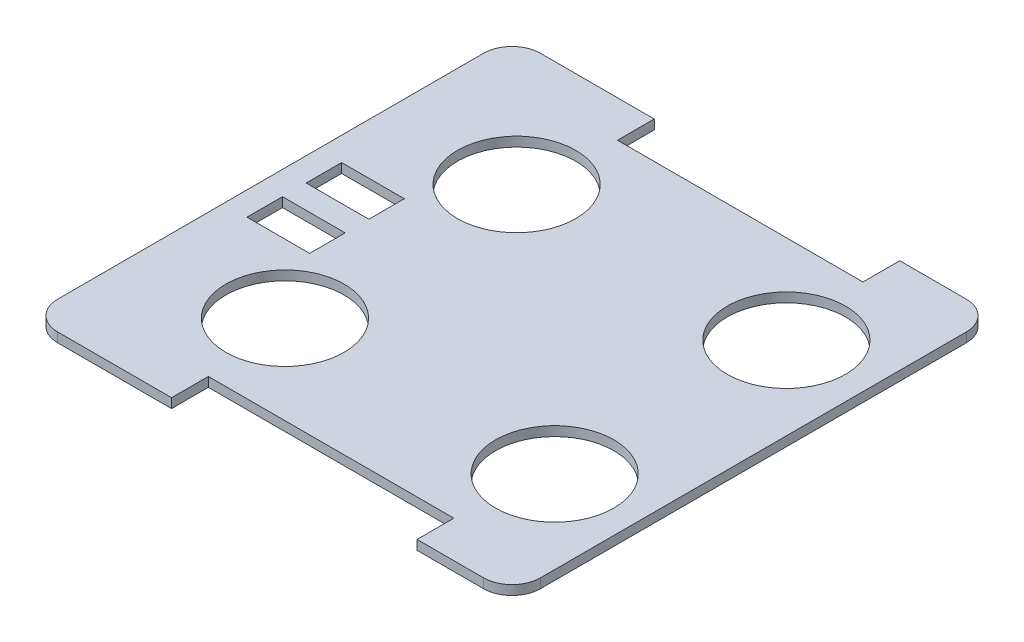
SolidWorks part; units mm, degrees
material "Aleación 1060"
ref_plane "Alzado" through (0, 0, 0) normal (0, 0, 1) x (1, 0, 0)
ref_plane "Planta" through (0, 0, 0) normal (0, 1, 0) x (1, 0, 0)
ref_plane "Vista lateral" through (0, 0, 0) normal (1, 0, 0) x (0, 0, -1)
ref_plane "Plano1" through (0, 54.7071, 0) normal (0, 1, 0) x (1, 0, 0)
sketch "Croquis1" plane through (0, 54.7071, 0) normal (0, 1, 0) x (1, 0, 0)
  line L48 (-135.857, -92.1) -> (-135.857, -55) construction
  line L55 (-135.857, -92.1) -> (71.653, -92.1) construction
  line L63 (71.653, -92.1) -> (71.653, -55) construction
  line L72 (71.653, -437.9) -> (71.653, -475) construction
  line L82 (-135.857, -437.9) -> (71.653, -437.9) construction
  line L93 (-135.857, -437.9) -> (-135.857, -475) construction
  line L105 (-232.102, -61.0045) -> (-135.857, -61.0045) construction
  line L106 (71.653, -61.0045) -> (127.898, -61.0045) construction
  line L107 (151.8935, -85) -> (151.8935, -445) construction
  line L108 (127.898, -468.9955) -> (71.653, -468.9955) construction
  line L109 (-135.857, -468.9955) -> (-232.102, -468.9955) construction
  line L110 (-256.0976, -445) -> (-256.0976, -85) construction
  line L111 (-135.857, -92.1) -> (71.653, -92.1)
  line L112 (71.653, -437.9) -> (71.653, -468.9955)
  line L113 (-135.857, -437.9) -> (71.653, -437.9)
  line L114 (-135.857, -437.9) -> (-135.857, -468.9955)
  line L115 (-135.857, -92.1) -> (-135.857, -61.0045)
  line L116 (71.653, -92.1) -> (71.653, -61.0045)
  line L117 (-232.102, -61.0045) -> (-135.857, -61.0045)
  line L118 (71.653, -61.0045) -> (127.898, -61.0045)
  line L119 (151.8935, -85) -> (151.8935, -445)
  line L120 (127.898, -468.9955) -> (71.653, -468.9955)
  line L121 (-135.857, -468.9955) -> (-232.102, -468.9955)
  line L122 (-256.0976, -445) -> (-256.0976, -85)
  arc A56 (-232.102, -61.0045) -> (-256.0976, -85) centre (-232.102, -85) ccw construction
  arc A57 (151.8935, -85) -> (127.898, -61.0045) centre (127.898, -85) ccw construction
  arc A58 (127.898, -468.9955) -> (151.8935, -445) centre (127.898, -445) ccw construction
  arc A59 (-256.0976, -445) -> (-232.102, -468.9955) centre (-232.102, -445) ccw construction
  arc A60 (-232.102, -61.0045) -> (-256.0976, -85) centre (-232.102, -85) ccw
  arc A61 (151.8935, -85) -> (127.898, -61.0045) centre (127.898, -85) ccw
  arc A62 (127.898, -468.9955) -> (151.8935, -445) centre (127.898, -445) ccw
  arc A63 (-256.0976, -445) -> (-232.102, -468.9955) centre (-232.102, -445) ccw
  point P1 (0, 0)
  point P2 (0, 0)
  point P16 (0, 0)
extrude "Saliente-Extruir1" add sketch "Croquis1" along normal mid plane 8
sketch "Croquis2" plane through (0, 58.7071, 0) normal (0, 1, 0) x (1, 0, 0)
  line L0 (-32.102, -92.1) -> (-32.102, -437.9) construction
  line L5 (71.653, -92.1) -> (-135.857, -92.1) construction
  line L6 (51.8935, -167.1) -> (111.8935, -167.1) construction
  line L11 (-256.0976, -265) -> (151.8935, -265) construction
  line L12 (-92.102, -92.1) -> (27.898, -92.1) construction
  line L13 (-92.102, -92.1) -> (-92.102, -244.5) construction
  line L14 (-92.102, -244.5) -> (27.898, -244.5) construction
  line L15 (27.898, -92.1) -> (27.898, -244.5) construction
  line L16 (-256.0976, -85) -> (-256.0976, -445) construction
  line L17 (151.8935, -445) -> (151.8935, -85) construction
  line L18 (-92.102, -285.5) -> (27.898, -285.5) construction
  line L19 (27.898, -437.9) -> (27.898, -285.5) construction
  line L20 (-92.102, -437.9) -> (27.898, -437.9) construction
  line L21 (-92.102, -437.9) -> (-92.102, -285.5) construction
  line L26 (111.8935, -237.1) -> (111.8935, -97.1) construction
  line L27 (51.8935, -97.1) -> (111.8935, -97.1) construction
  line L28 (51.8935, -237.1) -> (51.8935, -97.1) construction
  line L29 (51.8935, -237.1) -> (111.8935, -237.1) construction
  line L30 (-256.0976, -290) -> (-244.6304, -290) construction
  line L31 (-256.0976, -290) -> (-256.0976, -240) construction
  line L32 (-256.0976, -240) -> (-244.6304, -240) construction
  line L33 (-244.6304, -290) -> (-244.6304, -240) construction
  line L39 (-116.0976, -237.1) -> (-176.0976, -237.1) construction
  line L40 (-116.0976, -237.1) -> (-116.0976, -97.1) construction
  line L41 (-116.0976, -97.1) -> (-176.0976, -97.1) construction
  line L42 (-176.0976, -237.1) -> (-176.0976, -97.1) construction
  line L43 (-116.0976, -167.1) -> (-176.0976, -167.1) construction
  line L44 (51.8935, -292.9) -> (111.8935, -292.9) construction
  line L45 (51.8935, -292.9) -> (51.8935, -432.9) construction
  line L46 (51.8935, -432.9) -> (111.8935, -432.9) construction
  line L47 (111.8935, -292.9) -> (111.8935, -432.9) construction
  line L48 (51.8935, -362.9) -> (111.8935, -362.9) construction
  line L49 (-116.0976, -362.9) -> (-176.0976, -362.9) construction
  line L50 (-176.0976, -292.9) -> (-176.0976, -432.9) construction
  line L51 (-116.0976, -432.9) -> (-176.0976, -432.9) construction
  line L52 (-116.0976, -292.9) -> (-116.0976, -432.9) construction
  line L53 (-116.0976, -292.9) -> (-176.0976, -292.9) construction
  line L55 (-236.0976, -275) -> (-183.0976, -275)
  line L56 (-236.0976, -275) -> (-236.0976, -305)
  line L57 (-236.0976, -305) -> (-183.0976, -305)
  line L58 (-183.0976, -275) -> (-183.0976, -305)
  line L62 (-236.0976, -225) -> (-183.0976, -225)
  line L63 (-183.0976, -255) -> (-183.0976, -225)
  line L64 (-236.0976, -255) -> (-183.0976, -255)
  line L65 (-236.0976, -255) -> (-236.0976, -225)
  circle A0 centre (-146.0976, -167.1) radius 50
  circle A1 centre (81.8935, -167.1) radius 50
  circle A3 centre (81.8935, -362.9) radius 50
  circle A4 centre (-146.0976, -362.9) radius 50
  point P3 (-32.102, -437.9)
  point P44 (-256.0976, -265)
  point P51 (-32.102, -92.1)
  point P52 (-32.102, -92.1)
  point P61 (131.8935, -167.1)
  point P67 (-236.0976, -290)
  dimension "D6" = 100
  dimension "D1" = 60
  dimension "D2" = 140
  dimension "D3" = 152.4
  dimension "D4" = 120
  dimension "D5" = 50
  dimension "D7" = 20
  dimension "D8" = 53
  dimension "D9" = 30
  dimension "D10" = 20
  dimension "D11" = 75
extrude "Cortar-Extruir1" cut sketch "Croquis2" against normal up to next
